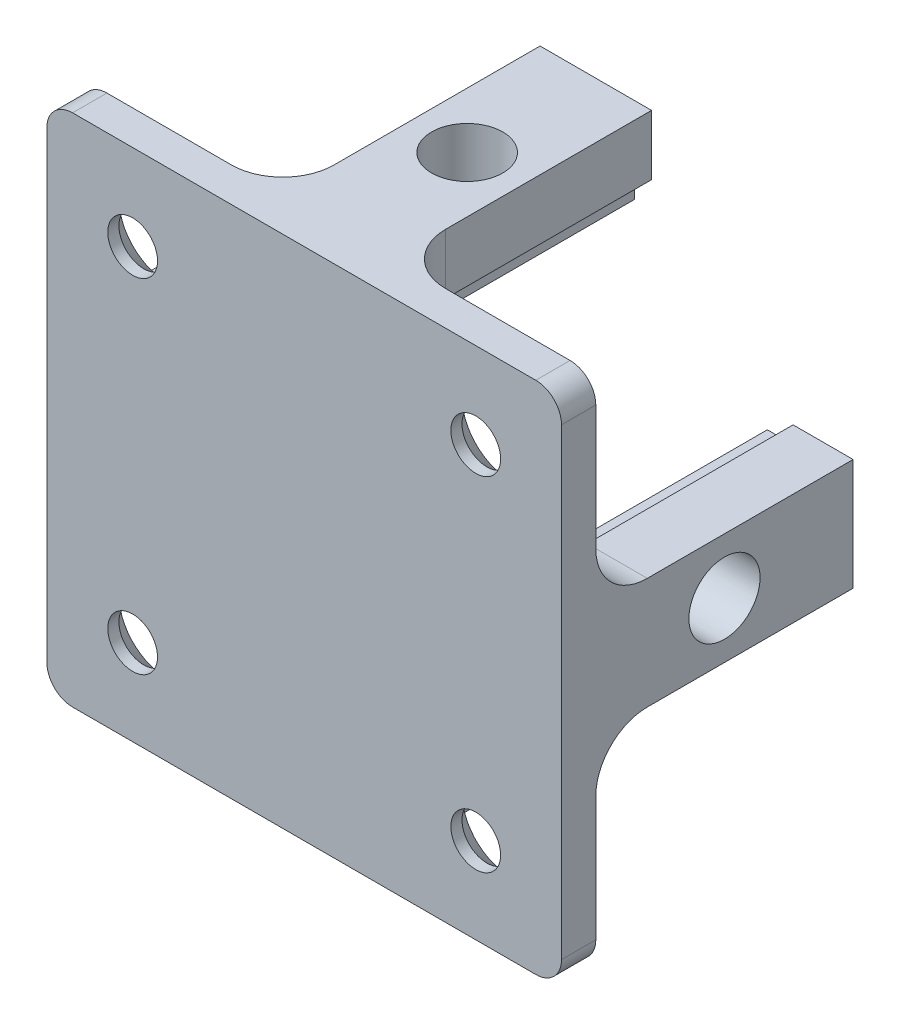
SolidWorks part; units mm, degrees
ref_plane "Front Plane" through (0, 0, 0) normal (0, 0, 1) x (1, 0, 0)
ref_plane "Top Plane" through (0, 0, 0) normal (0, 1, 0) x (1, 0, 0)
ref_plane "Right Plane" through (0, 0, 0) normal (1, 0, 0) x (0, 0, -1)
sketch "Sketch1" plane through (0, 0, 0) normal (0, 0, 1) x (1, 0, 0)
  line L0 (-45, 45) -> (0, 0) construction
  line L1 (-52.5, -7.5) -> (7.5, -7.5)
  line L2 (-52.5, -7.5) -> (-52.5, 52.5)
  line L3 (-52.5, 52.5) -> (7.5, 52.5)
  line L4 (7.5, -7.5) -> (7.5, 52.5)
  line L5 (-52.5, -7.5) -> (7.5, 52.5) construction
  line L6 (-52.5, 52.5) -> (7.5, -7.5) construction
  line L7 (0, 0) -> (-45, 0) construction
  line L8 (0, 0) -> (0, 45) construction
  line L9 (0, 45) -> (-45, 45) construction
  line L10 (-45, 0) -> (-45, 45) construction
  line L11 (0, 45) -> (-45, 0) construction
  line L12 (-29, 52.5) -> (-29, 45.5)
  line L13 (-52.5, 16) -> (-45.5, 16)
  line L14 (-52.5, 16) -> (-52.5, 29)
  line L15 (-52.5, 29) -> (-45.5, 29)
  line L16 (-45.5, 16) -> (-45.5, 29)
  line L17 (-45.5, 27) -> (-42.5, 27)
  line L18 (-45.5, 27) -> (-45.5, 18)
  line L19 (-45.5, 18) -> (-42.5, 18)
  line L20 (-42.5, 27) -> (-42.5, 18)
  line L21 (-29, 52.5) -> (-16, 52.5)
  line L22 (-16, 52.5) -> (-16, 45.5)
  line L23 (-29, 45.5) -> (-16, 45.5)
  line L24 (-18, 45.5) -> (-18, 42.5)
  line L25 (-18, 45.5) -> (-27, 45.5)
  line L26 (-27, 45.5) -> (-27, 42.5)
  line L27 (-18, 42.5) -> (-27, 42.5)
  line L28 (7.5, 29) -> (0.5, 29)
  line L29 (7.5, 29) -> (7.5, 16)
  line L30 (7.5, 16) -> (0.5, 16)
  line L31 (0.5, 29) -> (0.5, 16)
  line L32 (0.5, 18) -> (-2.5, 18)
  line L33 (0.5, 18) -> (0.5, 27)
  line L34 (0.5, 27) -> (-2.5, 27)
  line L35 (-2.5, 18) -> (-2.5, 27)
  line L36 (-16, -7.5) -> (-16, -0.5)
  line L37 (-16, -7.5) -> (-29, -7.5)
  line L38 (-29, -7.5) -> (-29, -0.5)
  line L39 (-16, -0.5) -> (-29, -0.5)
  line L40 (-27, -0.5) -> (-27, 2.5)
  line L41 (-27, -0.5) -> (-18, -0.5)
  line L42 (-18, -0.5) -> (-18, 2.5)
  line L43 (-27, 2.5) -> (-18, 2.5)
  point P0 (-22.5, 22.5)
  point P10 (-22.5, 22.5)
  point P19 (-52.5, 22.5)
  point P20 (-45.5, 22.5)
  point P21 (0, 0)
  point P22 (-2.5, 42.5)
  point P23 (0, 0)
  point P48 (0, 0)
  point P49 (-2.5, 2.5)
  point P50 (-42.5, 2.5)
  point P51 (-42.5, 42.5)
  dimension "D1" = 60
  dimension "D2" = 60
  dimension "D3" = 45
  dimension "D4" = 45
  dimension "D5" = 13
  dimension "D6" = 7
  dimension "D7" = 9
  dimension "D8" = 3
  dimension "D10" = 10
  dimension "D9" = 4
  dimension "D11" = 4
extrude "Boss-Extrude1" add sketch "Sketch1" along normal blind 4 contours L40 L43 L42 L39 L36 L1 L4 L30 L31 L32 L35 L34 L28 L3 L22 L23 L24 L27 L26 L12 L2 L15 L16 L17 L20 L19 L13 L38 | L13 L16 L15 L2 | L20 L17 L16 L19 | L12 L23 L22 L3 | L27 L24 L23 L26 | L35 L32 L31 L34 | L28 L31 L30 L4 | L43 L40 L39 L42 | L36 L39 L38 L1 region at (-22.5, 22.5, 0) region at (-22.5, -4, 0) region at (-49, 22.5, 0) region at (-22.5, 1, 0) region at (-44, 22.5, 0) region at (4, 22.5, 0) region at (-22.5, 49, 0) region at (-1, 22.5, 0) region at (-22.5, 44, 0)
extrude "Boss-Extrude2" add sketch "Sketch1<3>" against normal blind 30 contours L36 L39 L38 L1 | L43 L40 L39 L42 | L13 L16 L15 L2 | L20 L17 L16 L19 | L27 L24 L23 L26 | L12 L23 L22 L3 | L28 L31 L30 L4 | L35 L32 L31 L34 region at (-22.5, -4, 0) region at (-49, 22.5, 0) region at (-22.5, 1, 0) region at (-44, 22.5, 0) region at (4, 22.5, 0) region at (-22.5, 49, 0) region at (-1, 22.5, 0) region at (-22.5, 44, 0)
sketch "Sketch1<3>" plane through (0, 0, 0) normal (0, 0, 1) x (1, 0, 0) same geometry as "Sketch1"
hole_wizard "CSK for M5 Hex Socket Countersunk Cap Screw1" positions "Sketch6" profile "Sketch7" countersink size "M5" standard "ISO"
sketch "Sketch6" plane through (0, 0, 0) normal (0, 0, -1) x (-1, 0, 0)
  point P0 (2.5, 42.5)
  point P3 (42.5, 42.5)
  point P6 (42.5, 2.5)
  point P9 (2.5, 2.5)
sketch "Sketch7" plane through (-2.5, 42.5, 0) normal (1, 0, 0) x (0, 1, 0)
  line L0 (0, 0) -> (0, 5.7425)
  line L1 (0, 5.7425) -> (2.9, 4)
  line L2 (2.9, 4) -> (2.9, 2.7)
  line L3 (2.9, 2.7) -> (5.6, 0)
  line L5 (5.6, 0) -> (0, 0)
  line L6 (-2.9, 2.7) -> (-5.6, 0) construction
  line L10 (0, 5.7425) -> (-2.9, 4) construction
  line L11 (0, -6.35) -> (0, 107.95) construction
  dimension "Hole Dia." = 5.8
  dimension "Hole Depth" = 4
  dimension "Near C'Sink Dia." = 11.2
  dimension "Near C'Sink Angle" = 90
  dimension "Drill Angle" = 118
fillet "Fillet1" radius 3 4 edges at (-52.5, -7.5, 2) (7.5, -7.5, 2) (-52.5, 52.5, 2) (7.5, 52.5, 2)
fillet "Fillet2" radius 6 12 edges at (4, 16, 0) (4, 29, 0) (-16, 49, 0) (-29, 49, 0) (-49, 29, 0) (-49, 16, 0) (-29, -4, 0) (-16, -4, 0) (-22.5, 2.5, 0) (-42.5, 22.5, 0) (-22.5, 42.5, 0) (-2.5, 22.5, 0)
sketch "Sketch8" plane through (7.5, 0, 0) normal (1, 0, 0) x (0, 0, -1)
  line L0 (30, 22.5) -> (15, 22.5) construction
  line L1 (30, 16) -> (30, 29) construction
  circle A0 centre (15, 22.5) radius 4.15
  dimension "D2" = 8.3
  dimension "D1" = 15
extrude "Cut-Extrude1" cut sketch "Sketch8" against normal up to next
ref_axis "Axis1" through (-22.5, 22.5, 0) along (0, 0, -1)
pattern_circular "CirPattern1" count 4 over 360 about axis through (-22.5, 22.5, 0) along (0, 0, -1) of "Cut-Extrude1"
